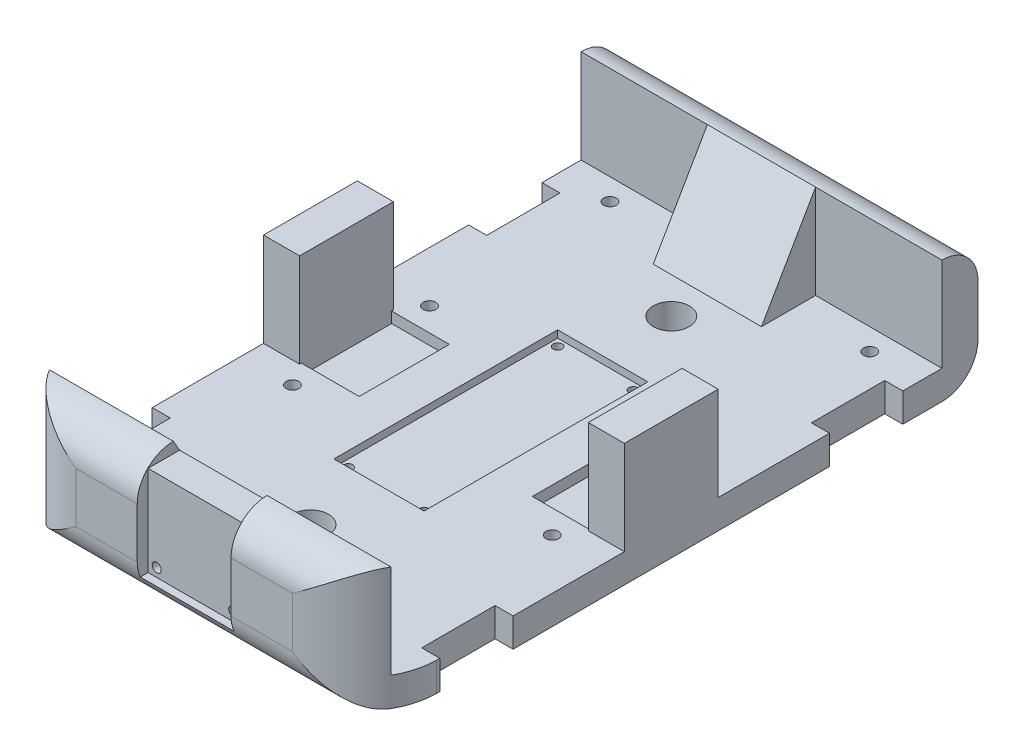
SolidWorks part; units mm, degrees
ref_plane "前视基准面" through (0, 0, 0) normal (0, 0, 1) x (1, 0, 0)
ref_plane "上视基准面" through (0, 0, 0) normal (0, 1, 0) x (1, 0, 0)
ref_plane "右视基准面" through (0, 0, 0) normal (1, 0, 0) x (0, 0, -1)
sketch "草图1" plane through (0, 0, 0) normal (0, 1, 0) x (1, 0, 0)
  line L0 (0, 0) -> (0, 8.8316) construction
  line L1 (-50, -75) -> (50, -75)
  line L2 (-50, -75) -> (-50, 75)
  line L3 (-50, 75) -> (50, 75)
  line L4 (50, -75) -> (50, 75)
  line L5 (-50, -75) -> (50, 75) construction
  line L6 (-50, 75) -> (50, -75) construction
  line L7 (0, 0) -> (12.2704, 0) construction
  point P0 (0, 0)
  dimension "D1" = 150
  dimension "D2" = 100
extrude "凸台-拉伸2" add sketch "草图1" along normal blind 8
sketch "草图3" plane through (0, 8, 0) normal (0, 1, 0) x (1, 0, 0)
  line L0 (-50, 75) -> (-50, -75) construction
  line L1 (-50, -75) -> (50, -75) construction
  circle A2 centre (-36, -19) radius 1.75
  circle A3 centre (-36, -69) radius 1.75
  dimension "D1" = 50
  dimension "D2" = 6
  dimension "D3" = 3.5
  dimension "D4" = 3.5
  dimension "D5" = 14
  dimension "D6" = 14
extrude "切除-拉伸1" cut sketch "草图3" against normal through all
mirror "镜向1" about plane through (0, 0, 0) normal (1, 0, 0) of "切除-拉伸1"
mirror "镜向2" about plane through (0, 0, 0) normal (0, 0, 1) of "镜向1", "切除-拉伸1"
sketch "草图4" plane through (0, 8, 0) normal (0, 1, 0) x (1, 0, 0)
  line L1 (-12.5, -31) -> (12.5, -31)
  line L2 (-12.5, -31) -> (-12.5, 31)
  line L3 (-12.5, 31) -> (12.5, 31)
  line L4 (12.5, -31) -> (12.5, 31)
  line L5 (-12.5, -31) -> (12.5, 31) construction
  line L6 (-12.5, 31) -> (12.5, -31) construction
  point P0 (0, 0)
  dimension "D1" = 25
  dimension "D2" = 62
extrude "切除-拉伸2" cut sketch "草图4" against normal blind 2
sketch "草图6" plane through (0, 6, 0) normal (0, 1, 0) x (1, 0, 0)
  line L0 (0, 0) -> (36.683, 0) construction
  line L1 (0, 0) -> (0, 25.2849) construction
  line L2 (-12.5, 31) -> (-12.5, -31) construction
  line L5 (12.5, 31) -> (-12.5, 31) construction
  circle A0 centre (-10.5, 29) radius 1.25
  circle A1 centre (10.5, 29) radius 1.25
  circle A2 centre (10.5, -29) radius 1.25
  circle A3 centre (-10.5, -29) radius 1.25
  dimension "D1" = 2.5
  dimension "D2" = 2
  dimension "D3" = 2
extrude "切除-拉伸3" cut sketch "草图6" against normal blind 3
sketch "草图7" plane through (0, 8, 0) normal (0, 1, 0) x (1, 0, 0)
  line L0 (-50, 75) -> (-50, -75) construction
  line L1 (-50, 13) -> (-40, 13)
  line L2 (-50, 13) -> (-50, -13)
  line L3 (-50, -13) -> (-40, -13)
  line L4 (-40, 13) -> (-40, -13)
  line L5 (50, 75) -> (-50, 75) construction
  line L6 (-50, -75) -> (50, -75) construction
  line L7 (0, 0) -> (0, 97.8588) construction
  line L8 (50, 13) -> (40, 13)
  line L9 (50, -13) -> (40, -13)
  line L10 (40, 13) -> (40, -13)
  line L11 (50, 13) -> (50, -13)
  dimension "D1" = 62
  dimension "D2" = 62
  dimension "D3" = 10
extrude "凸台-拉伸3" add sketch "草图7" along normal blind 26
sketch "草图8" plane through (0, 8, 0) normal (0, 1, 0) x (1, 0, 0)
  line L0 (50, 75) -> (-50, 75) construction
  line L1 (-15, 75) -> (15, 75)
  line L2 (-15, 75) -> (-15, 60)
  line L3 (-15, 60) -> (15, 60)
  line L4 (15, 75) -> (15, 60)
  line L5 (-50, 75) -> (-50, 13) construction
  line L6 (50, 13) -> (50, 75) construction
  line L7 (0, 0) -> (78.3185, 0) construction
  line L8 (15, -75) -> (15, -60)
  line L9 (-15, -75) -> (15, -75)
  line L10 (-15, -75) -> (-15, -60)
  line L11 (-15, -60) -> (15, -60)
  point P6 (-15, 67.5)
  dimension "D1" = 35
  dimension "D2" = 35
  dimension "D3" = 15
extrude "凸台-拉伸4" add sketch "草图8" along normal blind 26
sketch "草图9" plane through (0, 8, 0) normal (0, 1, 0) x (1, 0, 0)
  line L0 (0, 0) -> (-92.8673, 0) construction
  line L1 (-40, -12.5) -> (-24, -12.5)
  line L2 (-40, -12.5) -> (-40, 12.5)
  line L3 (-40, 12.5) -> (-24, 12.5)
  line L4 (-24, -12.5) -> (-24, 12.5)
  line L5 (-40, -12.5) -> (-24, 12.5) construction
  line L6 (-40, 12.5) -> (-24, -12.5) construction
  line L7 (-40, -13) -> (-40, 13) construction
  line L8 (0, 0) -> (0, 62.8559) construction
  line L9 (40, -12.5) -> (24, -12.5)
  line L10 (24, -12.5) -> (24, 12.5)
  line L11 (40, -12.5) -> (40, 12.5)
  line L12 (40, 12.5) -> (24, 12.5)
  point P0 (-32, 0)
  dimension "D1" = 16
  dimension "D2" = 25
  dimension "D3" = 0
extrude "切除-拉伸4" cut sketch "草图9" against normal blind 3
sketch "草图10" plane through (0, 8, 0) normal (0, 1, 0) x (1, 0, 0)
  line L0 (0, 0) -> (0, 56.1196) construction
sketch "草图11" plane through (0, 0, -75) normal (0, 0, -1) x (-1, 0, 0)
  line L1 (-50, 34) -> (50, 34)
  line L2 (-50, 34) -> (-50, 0)
  line L3 (-50, 0) -> (50, 0)
  line L4 (50, 34) -> (50, 0)
extrude "凸台-拉伸5" add sketch "草图11" along normal blind 10
sketch "草图12" plane through (0, 0, 75) normal (0, 0, 1) x (1, 0, 0)
  line L1 (-50, 34) -> (50, 34)
  line L2 (-50, 34) -> (-50, 0)
  line L3 (-50, 0) -> (50, 0)
  line L4 (50, 34) -> (50, 0)
extrude "凸台-拉伸6" add sketch "草图12" along normal blind 10
sketch "草图13" plane through (0, 0, 85) normal (0, 0, 1) x (1, 0, 0)
  line L0 (50, 34) -> (-50, 34) construction
  line L1 (-13, 6) -> (13, 6)
  line L2 (-13, 6) -> (-13, 34)
  line L3 (-13, 34) -> (13, 34)
  line L4 (13, 6) -> (13, 34)
  line L5 (-13, 6) -> (13, 34) construction
  line L6 (-13, 34) -> (13, 6) construction
  line L7 (0, 0) -> (0, 32.4005) construction
  line L8 (-50, 0) -> (50, 0) construction
  point P0 (0, 20)
  dimension "D1" = 28
  dimension "D2" = 26
extrude "切除-拉伸5" cut sketch "草图13" against normal blind 3
sketch "草图14" plane through (0, 0, 82) normal (0, 0, 1) x (1, 0, 0)
  line L0 (13, 34) -> (-13, 34) construction
  line L1 (-13, 37) -> (13, 37)
  line L2 (-13, 37) -> (-13, 31)
  line L3 (-13, 31) -> (13, 31)
  line L4 (13, 37) -> (13, 31)
  line L5 (-13, 37) -> (13, 31) construction
  line L6 (-13, 31) -> (13, 37) construction
  point P0 (0, 34)
  dimension "D1" = 6
  dimension "D2" = 26
extrude "切除-拉伸6" cut sketch "草图14" against normal up to next
sketch "草图17" plane through (-15, 0, 0) normal (-1, 0, 0) x (0, 0, 1)
  line L0 (75, 34) -> (60, 8)
  line L4 (60, 8) -> (75, 8)
  line L5 (75, 8) -> (75, 34)
  line L6 (75, 34) -> (60, 34)
  line L7 (60, 34) -> (60, 8)
  line L10 (75, 34) -> (60, 34)
  line L11 (60, 34) -> (60, 8)
  dimension "D1" = 0
extrude "切除-拉伸7" cut sketch "草图17" against normal up to next
sketch "草图18" plane through (-15, 0, 0) normal (-1, 0, 0) x (0, 0, 1)
  line L0 (-75, 34) -> (-60, 8)
  line L4 (-75, 8) -> (-60, 8)
  line L5 (-60, 8) -> (-60, 34)
  line L6 (-60, 34) -> (-75, 34)
  line L7 (-75, 34) -> (-75, 8)
  line L9 (-60, 8) -> (-60, 34)
  line L10 (-60, 34) -> (-75, 34)
  dimension "D1" = 0
extrude "切除-拉伸8" cut sketch "草图18" against normal up to next
sketch "草图19" plane through (0, 0, 82) normal (0, 0, 1) x (1, 0, 0)
  line L0 (0, 0) -> (0, 38.7412) construction
  line L1 (-13, 6) -> (13, 6) construction
  line L2 (-13, 34) -> (-13, 6) construction
  circle A0 centre (-10.6, 8.4) radius 1.25
  circle A1 centre (10.6, 8.4) radius 1.25
  dimension "D1" = 2.5
  dimension "D2" = 2.4
  dimension "D3" = 2.4
extrude "切除-拉伸9" cut sketch "草图19" against normal blind 3
sketch "草图20" plane through (0, 8, 0) normal (0, 1, 0) x (1, 0, 0)
  line L0 (-36, -19) -> (-36, -69) construction
  line L1 (-36, -44) -> (-19.4282, -44) construction
  line L2 (-50, -13) -> (-50, -75) construction
  line L3 (-50, -43.84) -> (-45, -43.84)
  line L4 (-50, -43.84) -> (-50, -64.16)
  line L5 (-50, -64.16) -> (-45, -64.16)
  line L6 (-45, -43.84) -> (-45, -64.16)
  line L7 (-36, -54) -> (-12.2494, -54) construction
  line L8 (-50, -75) -> (-15, -75) construction
  dimension "D1" = 5
  dimension "D2" = 20.32
  dimension "D3" = 10.84
  dimension "D4" = 10
extrude "切除-拉伸10" cut sketch "草图20" against normal blind 10
mirror "镜向3" about plane through (0, 0, 0) normal (0, 0, 1) of "切除-拉伸10"
mirror "镜向4" about plane through (0, 0, 0) normal (1, 0, 0) of "镜向3"
fillet "圆角1" radius 10 1 edges at (0, 0, 85)
fillet "圆角2" radius 10 2 edges at (31.5, 34, 85) (-31.5, 34, 85)
fillet "圆角3" radius 20 1 edges at (50, 17, 85) tangent propagation no
fillet "圆角4" radius 20 1 edges at (-50, 17, 85) tangent propagation no
fillet "圆角5" radius 10 2 edges at (0, 0, -85) (0, 34, -85)
sketch "草图21" plane through (0, 8, 0) normal (0, 1, 0) x (1, 0, 0)
  line L0 (0, 0) -> (20.0314, 0) construction
  circle A0 centre (0, 50) radius 5
  circle A1 centre (0, -50) radius 5
  dimension "D2" = 10
  dimension "D1" = 50
extrude "切除-拉伸11" cut sketch "草图21" against normal through all
